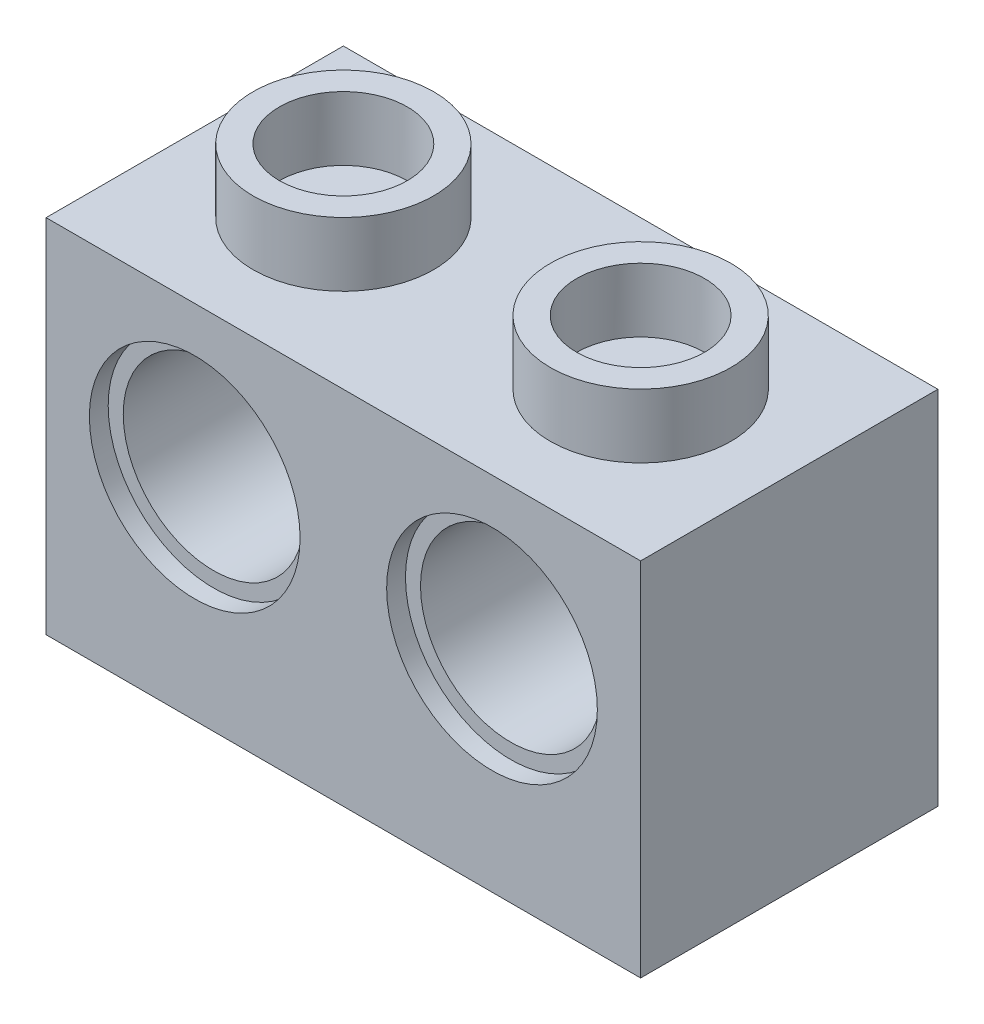
SolidWorks part; units mm, degrees
ref_plane "Front Plane" through (0, 0, 0) normal (0, 0, 1) x (1, 0, 0)
ref_plane "Top Plane" through (0, 0, 0) normal (0, 1, 0) x (1, 0, 0)
ref_plane "Right Plane" through (0, 0, 0) normal (1, 0, 0) x (0, 0, -1)
sketch "Sketch1" plane through (0, 0, 0) normal (0, 1, 0) x (1, 0, 0)
  line L1 (0, 0) -> (7.9, 0)
  line L2 (0, 0) -> (0, 7.9)
  line L3 (0, 7.9) -> (7.9, 7.9)
  line L4 (7.9, 0) -> (7.9, 7.9)
  dimension "D1" = 7.9
  dimension "D2" = 7.9
extrude "Boss-Extrude1" add sketch "Sketch1" along normal blind 9.6
sketch "Sketch2" plane through (0, 0, 0) normal (0, 0, 1) x (1, 0, 0)
  line L0 (3.95, 9.6) -> (3.95, 0) construction
  line L1 (0, 9.6) -> (7.9, 9.6) construction
  line L2 (0, 0) -> (7.9, 0) construction
  line L3 (3.95, 0) -> (3.95, 3.2)
  line L4 (3.95, 9.6) -> (3.95, 7.9983)
  line L5 (3.95, 3.2) -> (3.95, 7.9983)
  circle A0 centre (3.95, 5.5992) radius 2.8
  circle A1 centre (3.95, 5.5992) radius 2.4
  dimension "D2" = 4.8
  dimension "D3" = 5.6
  dimension "D1" = 3.2
extrude "Cut-Extrude1" cut sketch "Sketch2" against normal blind 9.6 contours L4 A1 L3 L5 | L3 A1 L4 L5 region at (2.9314, 5.5992, 0) region at (4.9686, 5.5992, 0)
sketch "Sketch3" plane through (0, 0, 0) normal (0, 0, 1) x (1, 0, 0)
  line L0 (3.95, 7.9992) -> (3.95, 3.1992)
  circle A0 centre (3.95, 5.5992) radius 2.4 construction
  circle A1 centre (3.95, 5.5992) radius 2.8
  circle M2 centre (3.95, 5.5992) radius 2.4
  dimension "D1" = 5.6
extrude "Cut-Extrude2" cut sketch "Sketch3" against normal blind 0.5 contours A1 L0 M2 region at (1.2292, 5.5992, 0)
sketch "Sketch4" plane through (0, 0, -7.9) normal (0, 0, -1) x (-1, 0, 0)
  line L0 (-3.95, 7.9992) -> (-3.95, 3.1992)
  circle A0 centre (-3.95, 5.5992) radius 2.4 construction
  circle A1 centre (-3.95, 5.5992) radius 2.8
  circle M2 centre (-3.95, 5.5992) radius 2.4
  dimension "D1" = 5.6
extrude "Cut-Extrude3" cut sketch "Sketch4" against normal blind 0.5 contours A1 M2 region at (6.6708, 5.5992, -7.9)
sketch "Sketch5" plane through (0, 9.6, 0) normal (0, 1, 0) x (1, 0, 0)
  line L0 (0, 7.9) -> (7.9, 0) construction
  circle A0 centre (3.95, 3.95) radius 2.4
  dimension "D1" = 4.8
extrude "Boss-Extrude2" add sketch "Sketch5" along normal blind 1.7
sketch "Sketch6" plane through (0, 11.3, 0) normal (0, 1, 0) x (1, 0, 0)
  line L0 (1.55, 3.95) -> (6.35, 3.95)
  circle A0 centre (3.95, 3.95) radius 2.4 construction
  circle A1 centre (3.95, 3.95) radius 2.4 construction
  circle A2 centre (3.95, 3.95) radius 1.7
  dimension "D1" = 3.4
extrude "Cut-Extrude4" cut sketch "Sketch6" against normal up to surface (1.7 mm away) contours L0 A2 | L0 A2 region at (3.95, 11.3, -4.6715) region at (3.95, 11.3, -3.2285) up to face at (3.95, 9.6, -1.55)
mirror "Mirror1" about plane through (7.9, 9.6, 0) normal (-1, 0, 0) of bodies 106
